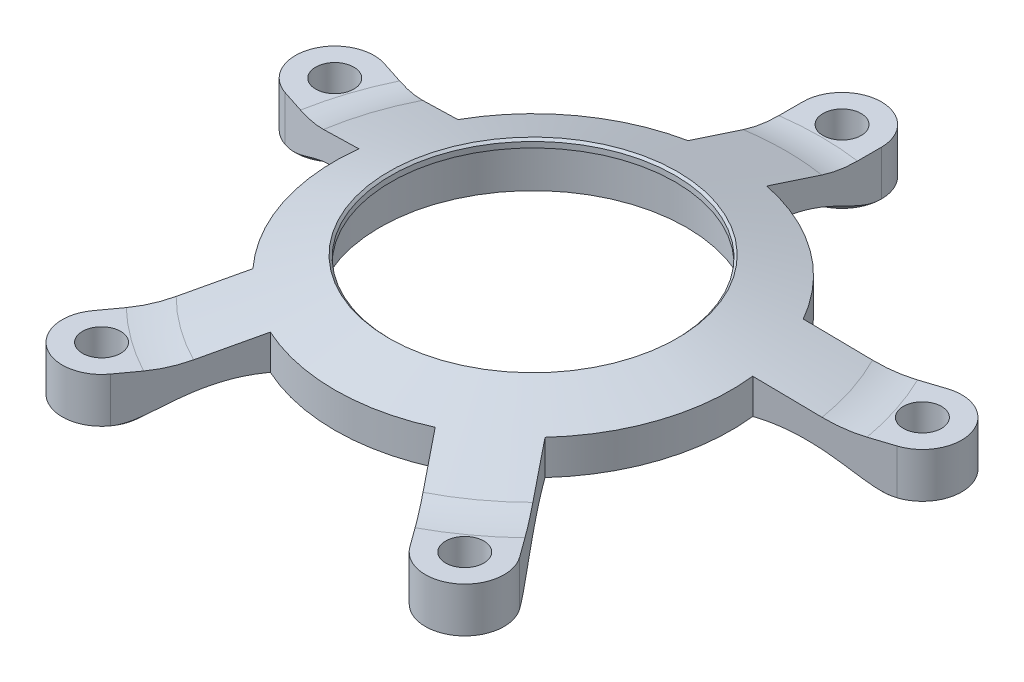
SolidWorks part; units mm, degrees
material "ABS"
ref_plane "Plan de face" through (0, 0, 0) normal (0, 0, 1) x (1, 0, 0)
ref_plane "Plan de dessus" through (0, 0, 0) normal (0, 1, 0) x (1, 0, 0)
ref_plane "Plan de droite" through (0, 0, 0) normal (1, 0, 0) x (0, 0, -1)
sketch "Esquisse1" plane through (0, 0, 0) normal (0, 1, 0) x (1, 0, 0)
  line L0 (-3.5, 27.5) -> (-3.5, 17.2995)
  line L1 (3.5, 27.5) -> (3.5, 17.2995)
  line L2 (25.0725, 11.8267) -> (15.3712, 8.6745)
  line L3 (27.2356, 5.1693) -> (17.5344, 2.0171)
  line L4 (18.9957, -20.1907) -> (12.9999, -11.9383)
  line L5 (13.3325, -24.3052) -> (7.3368, -16.0528)
  line L6 (-13.3325, -24.3052) -> (-7.3368, -16.0528)
  line L7 (-18.9957, -20.1907) -> (-12.9999, -11.9383)
  line L8 (-27.2356, 5.1693) -> (-17.5344, 2.0171)
  line L9 (-25.0725, 11.8267) -> (-15.3712, 8.6745)
  circle A0 centre (0, 0) radius 13.65
  arc A1 (-3.5, 17.2995) -> (-15.3712, 8.6745) centre (0, 0) ccw
  circle A2 centre (0, 0) radius 27.5 construction
  circle A3 centre (0, 27.5) radius 1.7
  arc A4 (3.5, 27.5) -> (-3.5, 27.5) centre (0, 27.5) ccw
  circle A5 centre (0, 0) radius 31 construction
  circle A6 centre (26.1541, 8.498) radius 1.7
  arc A7 (27.2356, 5.1693) -> (25.0725, 11.8267) centre (26.1541, 8.498) ccw
  circle A8 centre (16.1641, -22.248) radius 1.7
  arc A9 (13.3325, -24.3052) -> (18.9957, -20.1907) centre (16.1641, -22.248) ccw
  circle A10 centre (-16.1641, -22.248) radius 1.7
  arc A11 (-18.9957, -20.1907) -> (-13.3325, -24.3052) centre (-16.1641, -22.248) ccw
  circle A12 centre (-26.1541, 8.498) radius 1.7
  arc A13 (-25.0725, 11.8267) -> (-27.2356, 5.1693) centre (-26.1541, 8.498) ccw
  arc A14 (-17.5344, 2.0171) -> (-12.9999, -11.9383) centre (0, 0) ccw
  arc A15 (15.3712, 8.6745) -> (3.5, 17.2995) centre (0, 0) ccw
  arc A16 (12.9999, -11.9383) -> (17.5344, 2.0171) centre (0, 0) ccw
  arc A17 (-7.3368, -16.0528) -> (7.3368, -16.0528) centre (0, 0) ccw
  point P43 (0, 0)
  dimension "D1" = 27.3
  dimension "D2" = 4
  dimension "D3" = 55
  dimension "D4" = 3.4
  dimension "D5" = 62
  dimension "D6" = 5
extrude "Boss.-Extru.1" add sketch "Esquisse1" along normal blind 4
sketch "Esquisse2" plane through (0, 4, 0) normal (0, 1, 0) x (1, 0, 0)
  line L10 (-3.5, 27.5) -> (-3.5, 17.2995)
  line L11 (-15.3712, 8.6745) -> (-25.0725, 11.8267)
  line L12 (-27.2356, 5.1693) -> (-17.5344, 2.0171)
  line L13 (-12.9999, -11.9383) -> (-18.9957, -20.1907)
  line L14 (-13.3325, -24.3052) -> (-7.3368, -16.0528)
  line L15 (7.3368, -16.0528) -> (13.3325, -24.3052)
  line L16 (18.9957, -20.1907) -> (12.9999, -11.9383)
  line L17 (17.5344, 2.0171) -> (27.2356, 5.1693)
  line L18 (25.0725, 11.8267) -> (15.3712, 8.6745)
  line L19 (3.5, 17.2995) -> (3.5, 27.5)
  line L20 (-3.5, 27.5) -> (-3.5, 17.2995)
  line L21 (-15.3712, 8.6745) -> (-25.0725, 11.8267)
  line L22 (-27.2356, 5.1693) -> (-17.5344, 2.0171)
  line L23 (-12.9999, -11.9383) -> (-18.9957, -20.1907)
  line L24 (-13.3325, -24.3052) -> (-7.3368, -16.0528)
  line L25 (7.3368, -16.0528) -> (13.3325, -24.3052)
  line L26 (18.9957, -20.1907) -> (12.9999, -11.9383)
  line L27 (17.5344, 2.0171) -> (27.2356, 5.1693)
  line L28 (25.0725, 11.8267) -> (15.3712, 8.6745)
  line L29 (3.5, 17.2995) -> (3.5, 27.5)
  circle A0 centre (16.1641, -22.248) radius 1.7 construction
  circle A1 centre (26.1541, 8.498) radius 1.7 construction
  circle A2 centre (0, 27.5) radius 1.7 construction
  circle A3 centre (-16.1641, -22.248) radius 1.7 construction
  circle A4 centre (-26.1541, 8.498) radius 1.7 construction
  circle A5 centre (16.1641, -22.248) radius 1.7
  circle A6 centre (26.1541, 8.498) radius 1.7
  circle A7 centre (0, 27.5) radius 1.7
  circle A8 centre (-16.1641, -22.248) radius 1.7
  circle A9 centre (-26.1541, 8.498) radius 1.7
  arc A10 (3.5, 27.5) -> (-3.5, 27.5) centre (0, 27.5) ccw
  arc A11 (-3.5, 17.2995) -> (-15.3712, 8.6745) centre (0, 0) ccw
  arc A12 (-25.0725, 11.8267) -> (-27.2356, 5.1693) centre (-26.1541, 8.498) ccw
  arc A13 (-17.5344, 2.0171) -> (-12.9999, -11.9383) centre (0, 0) ccw
  arc A14 (-18.9957, -20.1907) -> (-13.3325, -24.3052) centre (-16.1641, -22.248) ccw
  arc A15 (-7.3368, -16.0528) -> (7.3368, -16.0528) centre (0, 0) ccw
  arc A16 (13.3325, -24.3052) -> (18.9957, -20.1907) centre (16.1641, -22.248) ccw
  arc A17 (12.9999, -11.9383) -> (17.5344, 2.0171) centre (0, 0) ccw
  arc A18 (27.2356, 5.1693) -> (25.0725, 11.8267) centre (26.1541, 8.498) ccw
  arc A19 (15.3712, 8.6745) -> (3.5, 17.2995) centre (0, 0) ccw
  arc A20 (3.5, 27.5) -> (-3.5, 27.5) centre (0, 27.5) ccw
  arc A21 (-3.5, 17.2995) -> (-15.3712, 8.6745) centre (0, 0) ccw
  arc A22 (-25.0725, 11.8267) -> (-27.2356, 5.1693) centre (-26.1541, 8.498) ccw
  arc A23 (-17.5344, 2.0171) -> (-12.9999, -11.9383) centre (0, 0) ccw
  arc A24 (-18.9957, -20.1907) -> (-13.3325, -24.3052) centre (-16.1641, -22.248) ccw
  arc A25 (-7.3368, -16.0528) -> (7.3368, -16.0528) centre (0, 0) ccw
  arc A26 (13.3325, -24.3052) -> (18.9957, -20.1907) centre (16.1641, -22.248) ccw
  arc A27 (12.9999, -11.9383) -> (17.5344, 2.0171) centre (0, 0) ccw
  arc A28 (27.2356, 5.1693) -> (25.0725, 11.8267) centre (26.1541, 8.498) ccw
  arc A29 (15.3712, 8.6745) -> (3.5, 17.2995) centre (0, 0) ccw
  circle A30 centre (0, 0) radius 12.65
  circle A31 centre (0, 0) radius 13.65 construction
  dimension "D2" = 1
  dimension "D1" = 0
extrude "Boss.-Extru.2" add sketch "Esquisse2" along normal blind 1
sketch "Esquisse3" plane through (0, 0, 0) normal (0, -1, 0) x (1, 0, 0)
  circle A0 centre (-16.1641, 22.248) radius 1.7 construction
  circle A1 centre (-26.1541, -8.498) radius 1.7 construction
  circle A2 centre (0, -27.5) radius 1.7 construction
  circle A3 centre (26.1541, -8.498) radius 1.7 construction
  circle A4 centre (16.1641, 22.248) radius 1.7 construction
  circle A5 centre (-16.1641, 22.248) radius 1.7
  circle A6 centre (-26.1541, -8.498) radius 1.7
  circle A7 centre (0, -27.5) radius 1.7
  circle A8 centre (26.1541, -8.498) radius 1.7
  circle A9 centre (16.1641, 22.248) radius 1.7
  circle A10 centre (16.1641, 22.248) radius 3.5
  circle A11 centre (26.1541, -8.498) radius 3.5
  circle A12 centre (0, -27.5) radius 3.5
  circle A13 centre (-26.1541, -8.498) radius 3.5
  circle A14 centre (-16.1641, 22.248) radius 3.5
extrude "Boss.-Extru.3" add sketch "Esquisse3" along normal blind 3
fillet "Congé1" radius 10 5 edges at (-22.8254, 0, -7.4164) (-14.1068, 0, 19.4164) (0, 0, -24) (22.8254, 0, -7.4164) (14.1068, 0, 19.4164)
chamfer "Chanfrein1" distance 0.5 angle 45 1 edges at (0, 5, 12.65)
sketch "Esquisse4" plane through (0, 0, 0) normal (1, 0, 0) x (0, 0, -1)
  line L0 (0, 0) -> (0, 13.3038) construction
  line L1 (0, 5) -> (-11.9383, 5)
  line L2 (2.0171, 5) -> (-11.9383, 5) construction
  line L3 (-11.9383, 5) -> (-24, 1)
  line L5 (-24, 1) -> (-32, 1)
  line L7 (-32, 1) -> (-32, 6)
  line L8 (-32, 6) -> (0, 6)
  line L9 (0, 6) -> (0, 5)
  line L10 (-20.1907, 5) -> (-25.748, 5) construction
  point P13 (0, 0)
  point P19 (0, 0)
  dimension "D1" = 1
  dimension "D2" = 4
  dimension "D3" = 32
  dimension "D4" = 8
revolve "Enlèvement de matière-Révolution3" cut sketch "Esquisse4" angle 360 about L0
fillet "Congé2" radius 10 5 edges at (-22.8254, 1, -7.4164) (0, 1, -24) (22.8254, 1, -7.4164) (14.1068, 1, 19.4164) (-14.1068, 1, 19.4164)
